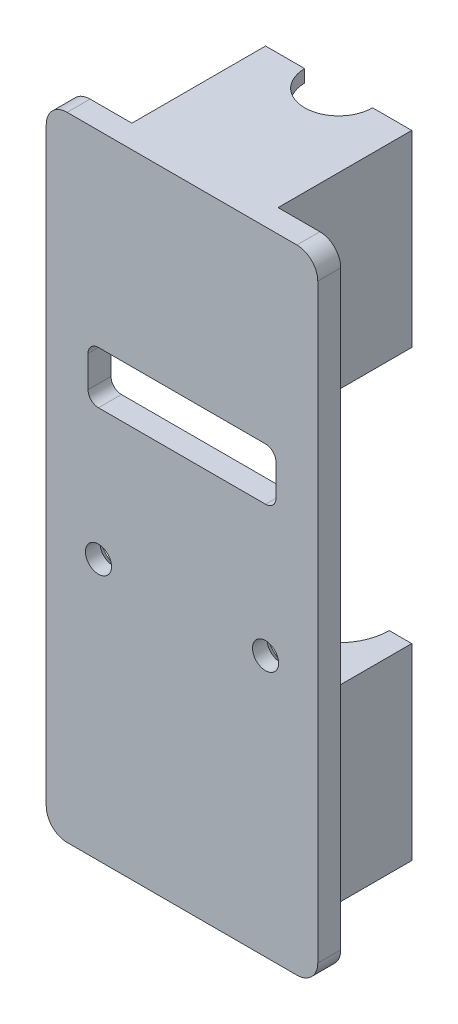
SolidWorks part; units mm, degrees
ref_plane "Front Plane" through (0, 0, 0) normal (0, 0, 1) x (1, 0, 0)
ref_plane "Top Plane" through (0, 0, 0) normal (0, 1, 0) x (1, 0, 0)
ref_plane "Right Plane" through (0, 0, 0) normal (1, 0, 0) x (0, 0, -1)
sketch "Sketch1" plane through (0, 0, 0) normal (0, 0, 1) x (1, 0, 0)
  line L0 (-16.25, 35.3459) -> (-16.25, 15.3459) construction
  line L1 (-16.25, 37.8459) -> (16.25, 37.8459)
  line L2 (-16.25, 37.8459) -> (-16.25, -37.8459)
  line L3 (-16.25, -37.8459) -> (16.25, -37.8459)
  line L4 (16.25, 37.8459) -> (16.25, -37.8459)
  line L5 (16.25, 0) -> (44.5824, 0) construction
  line L6 (8.75, -37.8459) -> (13.75, -37.8459) construction
  line L7 (16.25, -35.3459) -> (16.25, -15.3459) construction
  circle A1 centre (12.5, 34.0959) radius 2.6
  circle A2 centre (-12.5, 34.0959) radius 2.6
  circle A4 centre (-12.5, 34.0959) radius 2.6
  circle A5 centre (12.5, 26.5959) radius 2.6
  circle A6 centre (12.5, 19.0959) radius 2.6
  circle A7 centre (-12.5, 26.5959) radius 2.6
  circle A8 centre (-12.5, 19.0959) radius 2.6
  circle A9 centre (-12.5, -19.0959) radius 2.6
  circle A10 centre (-12.5, -26.5959) radius 2.6
  circle A11 centre (12.5, -19.0959) radius 2.6
  circle A12 centre (12.5, -26.5959) radius 2.6
  circle A13 centre (-12.5, -34.0959) radius 2.6
  circle A14 centre (12.5, -34.0959) radius 2.6
  dimension "D1" = 0.1
  dimension "D2" = 2
  dimension "D3" = 3
extrude "Boss-Extrude1" add sketch "Sketch1" along normal blind 2
extrude "Boss-Extrude2" add sketch "Sketch1<2>" along normal blind 0.75 from surface contours L1 L4 L3 L2 starting at face at (-15.1, -34.0959, 2)
sketch "Sketch1<2>" plane through (0, 0, 0) normal (0, 0, 1) x (1, 0, 0) same geometry as "Sketch1"
sketch "Sketch6" plane through (0, 0, 2.75) normal (0, 0, 1) x (1, 0, 0)
  line L0 (-10, -6.5959) -> (10, -6.5959)
  line L1 (16.25, -37.8459) -> (-16.25, -37.8459) construction
  circle A0 centre (10, -6.5959) radius 1.5625
  circle A1 centre (-10, -6.5959) radius 1.5625
  point P3 (0, -6.5959)
  dimension "D2" = 3.125
  dimension "D1" = 20
  dimension "D3" = 31.25
extrude "Cut-Extrude5" cut sketch "Sketch6" against normal through all contours A0 | A1 region at (10, -5.0776, 2.75) region at (-11.5183, -6.5959, 2.75)
ref_axis "Axis1" through (0, 0, 4.2125) along (0, 0, -1)
sketch "Sketch2" plane through (0, 0, 0) normal (0, 0, -1) x (-1, 0, 0)
  line L0 (16.25, -37.8459) -> (-16.25, -37.8459) construction
  line L1 (8.75, -15.3459) -> (-8.75, -15.3459)
  line L2 (8.75, -15.3459) -> (8.75, -37.8459)
  line L3 (8.75, -37.8459) -> (-8.75, -37.8459)
  line L4 (-8.75, -15.3459) -> (-8.75, -37.8459)
  line L5 (-8.75, -15.3459) -> (-8.75, -37.8459) construction
extrude "Boss-Extrude3" add sketch "Sketch2" along normal up to surface (16 mm away) up to face at (11.5625, -6.5959, 0)
sketch "Sketch7" plane through (0, -15.3459, 0) normal (0, 1, 0) x (1, 0, 0)
  line L0 (8.75, 16) -> (-8.75, 16) construction
  circle A0 centre (0, 16) radius 4.0625
  circle A1 centre (0, 16) radius 6.0625
  line M3 (8.75, 16) -> (-8.75, 16)
  dimension "D1" = 8.125
  dimension "D2" = 12.125
extrude "Cut-Extrude6" cut sketch "Sketch7" against normal through all contours A0 M3 region at (0, -15.3459, -14.2758)
extrude "Cut-Extrude7" cut sketch "Sketch7<3>" against normal blind 3.5
sketch "Sketch7<3>" plane through (0, -15.3459, 0) normal (0, 1, 0) x (1, 0, 0) same geometry as "Sketch7"
pattern_linear "LPattern3" count 3 spacing 8.75 along (0, -1, 0) of "Cut-Extrude7"
pattern_circular "CirPattern3" count 2 over 360 about axis through (0, 0, 4.2125) along (0, 0, -1) of "Boss-Extrude3", "Cut-Extrude6", "Cut-Extrude7", "LPattern3" reverse direction yes
sketch "Sketch8" plane through (0, 0, 0) normal (0, 0, -1) x (-1, 0, 0)
  line L0 (-6.0625, 15.3459) -> (-8.75, 15.3459) construction
  line L1 (11.25, 9.0959) -> (-11.25, 9.0959)
  line L2 (11.25, 9.0959) -> (11.25, 15.3459)
  line L3 (11.25, 15.3459) -> (-11.25, 15.3459)
  line L4 (-11.25, 9.0959) -> (-11.25, 15.3459)
  line L5 (11.25, 9.0959) -> (-11.25, 15.3459) construction
  line L6 (11.25, 15.3459) -> (-11.25, 9.0959) construction
  point P0 (0, 12.2209)
  dimension "D1" = 6.25
  dimension "D2" = 22.5
extrude "Cut-Extrude8" cut sketch "Sketch8" against normal through all
sketch "Sketch11" plane through (0, 0, 0) normal (0, 1, 0) x (1, 0, 0)
  line L0 (-4.0625, 16) -> (4.0625, 16) construction
  line L1 (-8.629, 16) -> (8.629, 16)
  arc A0 (-4.0625, 16) -> (4.0625, 16) centre (0, 16) ccw construction
  circle A1 centre (0, 16) radius 4.0625
  circle A2 centre (0, 16) radius 6.125
  point P13 (0, 16)
  dimension "D1" = 8.125
  dimension "D2" = 12.25
extrude "Boss-Extrude4" add sketch "Sketch11" along normal blind 0.25 from surface contours L1 A2 A1 region at (5.0938, 0, -15.863) starting at face at (0, -18.8459, -13.4688)
extrude "Boss-Extrude6" add sketch "Sketch11<3>" against normal blind 0.25 from surface contours L1 A2 A1 region at (5.0938, 0, -15.863) starting at face at (0, 18.8459, -13.4688)
sketch "Sketch11<3>" plane through (0, 0, 0) normal (0, 1, 0) x (1, 0, 0) same geometry as "Sketch11"
fillet "Fillet1" radius 2.5 4 edges at (-16.25, -37.8459, 1.375) (16.25, -37.8459, 1.375) (16.25, 37.8459, 1.375) (-16.25, 37.8459, 1.375)
fillet "Fillet2" radius 1.25 4 edges at (-11.25, 9.0959, 1.375) (-11.25, 15.3459, 1.375) (11.25, 9.0959, 1.375) (11.25, 15.3459, 1.375)
chamfer "Chamfer1" distance 1 angle 45 2 edges at (11.5625, -6.5959, 0) (-8.4375, -6.5959, 0)
